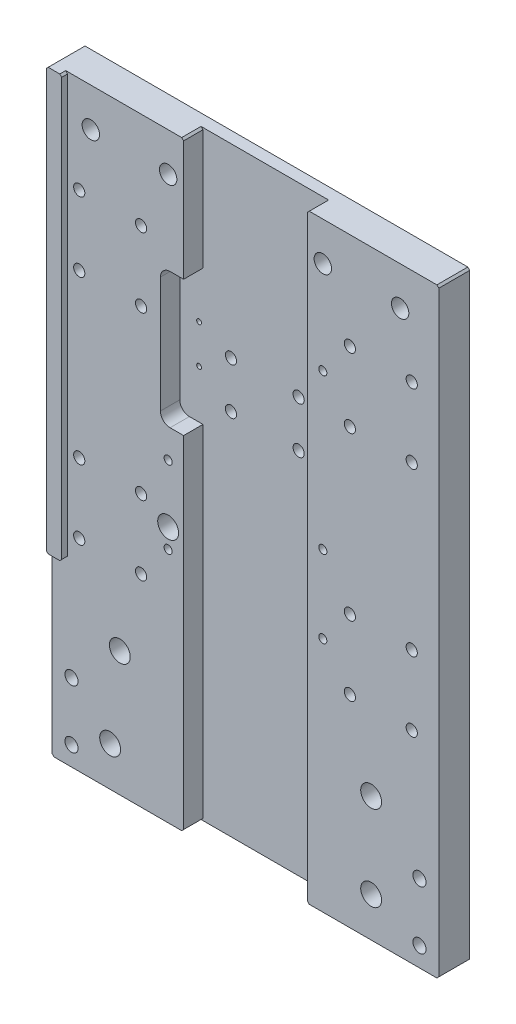
SolidWorks part; units mm, degrees
material "6061-T6 (SS)"
ref_plane "Front Plane" through (0, 0, 0) normal (0, 0, 1) x (1, 0, 0)
ref_plane "Top Plane" through (0, 0, 0) normal (0, 1, 0) x (1, 0, 0)
ref_plane "Right Plane" through (0, 0, 0) normal (1, 0, 0) x (0, 0, -1)
sketch "Sketch1" plane through (0, 0, 0) normal (0, 0, 1) x (1, 0, 0)
  line L0 (0, -10.4775) -> (0, 10.4775) construction
  line L1 (-70, 60) -> (70, 60) construction
  line L2 (-70, 60) -> (-70, -60) construction
  line L3 (-70, -60) -> (70, -60) construction
  line L4 (70, 60) -> (70, -60) construction
  line L5 (-70, 60) -> (70, -60) construction
  line L6 (-70, -60) -> (70, 60) construction
  line L7 (-86, 78) -> (-54, 78) construction
  line L8 (-86, 78) -> (-86, 42) construction
  line L9 (-86, 42) -> (-54, 42) construction
  line L10 (-54, 78) -> (-54, 42) construction
  line L11 (-86, 78) -> (-54, 42) construction
  line L12 (-86, 42) -> (-54, 78) construction
  line L13 (-100, 128) -> (100, 128)
  line L14 (-100, 128) -> (-100, -182.5)
  line L15 (-100, -182.5) -> (100, -182.5)
  line L16 (100, 128) -> (100, -182.5)
  line L17 (-100, -97.5) -> (100, -97.5) construction
  line L18 (-100, 88) -> (100, 88) construction
  line L19 (54, -42) -> (86, -42) construction
  line L20 (54, -42) -> (54, -78) construction
  line L21 (54, -78) -> (86, -78) construction
  line L22 (86, -42) -> (86, -78) construction
  line L23 (54, -42) -> (86, -78) construction
  line L24 (54, -78) -> (86, -42) construction
  line L25 (35.5, -12.5) -> (54.5, -12.5) construction
  line L26 (-17.5, 32) -> (17.5, 32) construction
  line L27 (-17.5, 32) -> (-17.5, 8) construction
  line L28 (-17.5, 8) -> (17.5, 8) construction
  line L29 (17.5, 32) -> (17.5, 8) construction
  line L30 (-17.5, 32) -> (17.5, 8) construction
  line L31 (-17.5, 8) -> (17.5, 32) construction
  line L32 (-100, -97.5) -> (100, -182.5) construction
  point P0 (0, 0)
  point P14 (0, -182.5)
  point P23 (0, 20)
  point P33 (0, -140)
  point P35 (45, -12.5)
  dimension "D1" = 120
  dimension "D2" = 140
  dimension "D3" = 36
  dimension "D4" = 32
  dimension "D5" = 85
  dimension "D6" = 19.5
  dimension "D7" = 40
  dimension "D8" = 10
  dimension "D9" = 200
  dimension "D10" = 24
  dimension "D11" = 35
  dimension "D12" = 20
  dimension "D13" = 19
  dimension "D14" = 45
  dimension "D15" = 47.5
  dimension "D16" = 140
  dimension "D17" = 310.5
extrude "Boss-Extrude1" add sketch "Sketch1" along normal blind 19.05
sketch "Sketch2" plane through (0, 0, 19.05) normal (0, 0, 1) x (1, 0, 0)
  line L0 (100, 128) -> (-100, 128) construction
  line L1 (-92, 128) -> (100, 128)
  line L2 (-92, 128) -> (-92, -90)
  line L3 (-100, -182.5) -> (100, -182.5)
  line L4 (100, 128) -> (100, -182.5)
  line L5 (-92, -90) -> (-100, -90)
  line L6 (-100, 128) -> (-100, -182.5) construction
  line L7 (-70, 60) -> (-70, -60) construction
  line L8 (-100, -90) -> (-100, -182.5)
  line L9 (-70, -60) -> (70, -60) construction
  dimension "D1" = 22
  dimension "D2" = 30
extrude "Cut-Extrude1" cut sketch "Sketch2" against normal offset from surface (3.05 mm away) 16 up to face at (0, -27.25, 0)
sketch "Sketch3" plane through (0, 0, 16) normal (0, 0, 1) x (1, 0, 0)
  line L0 (-100, 128) -> (100, 128) construction
  line L1 (-32, 128) -> (32, 128)
  line L2 (-32, 128) -> (-32, 65)
  line L3 (-32, -182.5) -> (32, -182.5)
  line L4 (32, 128) -> (32, -182.5)
  line L5 (-100, -182.5) -> (100, -182.5) construction
  line L6 (0, -10.4775) -> (0, 10.4775) construction
  line L7 (-32, 65) -> (-39, 65)
  line L8 (-44, 60) -> (-44, 0)
  line L9 (-39, -5) -> (-32, -5)
  line L10 (-32, -5) -> (-32, -182.5)
  line L12 (-34, 40) -> (-34, 20) construction
  line L13 (-44, 30) -> (-34, 30) construction
  arc A0 (-44, 0) -> (-39, -5) centre (-39, 0) ccw
  arc A1 (-39, 65) -> (-44, 60) centre (-39, 60) ccw
  point P8 (0, -182.5)
  point P20 (-44, -5)
  point P23 (-44, 65)
  dimension "D4" = 5
  dimension "D1" = 64
  dimension "D2" = 34
  dimension "D3" = 70
  dimension "D5" = 20
  dimension "D6" = 10
  dimension "D7" = 30
extrude "Cut-Extrude2" cut sketch "Sketch3" against normal blind 10
hole_wizard "M5 Clearance Hole2" positions "Sketch4" profile "Sketch5" hole size "M5" standard "ANSI Metric" end condition up to next
sketch "Sketch4" plane through (0, 0, 16) normal (0, 0, 1) x (1, 0, 0)
  point P0 (54, -42)
  point P3 (86, -42)
  point P6 (86, -78)
  point P9 (54, -78)
sketch "Sketch5" plane through (54, -42, 16) normal (1, 0, 0) x (0, -1, 0)
  line L0 (0, 0) -> (0, 16)
  line L1 (0, 16) -> (2.9, 16)
  line L2 (2.9, 16) -> (2.9, 0)
  line L5 (2.9, 0) -> (0, 0)
  line L11 (0, -6.35) -> (0, 107.95) construction
  dimension "Thru Hole Dia." = 5.8
  dimension "Thru Hole Depth" = 16
mirror "Mirror1" about plane through (0, 0, 0) normal (0, 1, 0) of "M5 Clearance Hole2"
hole_wizard "M8 Clearance Hole1" positions "Sketch13" profile "Sketch14" hole size "M8" standard "ANSI Metric" end condition up to next
sketch "Sketch13" plane through (0, 0, 16) normal (0, 0, 1) x (1, 0, 0)
  line L0 (40, 108) -> (80, 108)
  line L2 (-100, 88) -> (100, 88) construction
  line L3 (0, -10.4775) -> (0, 10.4775) construction
  point P1 (40, 108)
  point P2 (80, 108)
  dimension "D1" = 20
  dimension "D2" = 40
  dimension "D3" = 40
sketch "Sketch14" plane through (40, 108, 16) normal (1, 0, 0) x (0, -1, 0)
  line L0 (0, 0) -> (0, 16)
  line L1 (0, 16) -> (4.5, 16)
  line L2 (4.5, 16) -> (4.5, 0)
  line L5 (4.5, 0) -> (0, 0)
  line L11 (0, -6.35) -> (0, 107.95) construction
  dimension "Thru Hole Dia." = 9
  dimension "Thru Hole Depth" = 16
hole_wizard "M5x0.8 Tapped Hole1" positions "Sketch15" profile "Sketch16" tap size "M5x0.8" standard "ANSI Metric" end condition up to next
sketch "Sketch15" plane through (0, 0, 16) normal (0, 0, 1) x (1, 0, 0)
  line L0 (40, 60) -> (40, -20)
  line L1 (40, -20) -> (40, -60)
  line L3 (-70, -60) -> (70, -60) construction
  line L4 (-70, 60) -> (70, 60) construction
  point P0 (40, 60)
  point P1 (40, -20)
  point P3 (40, -60)
  dimension "D1" = 40
  dimension "D2" = 80
  dimension "D3" = 40
sketch "Sketch16" plane through (40, 60, 16) normal (1, 0, 0) x (0, -1, 0)
  line L0 (0, 0) -> (0, 16)
  line L1 (0, 16) -> (2.1, 16)
  line L2 (2.1, 16) -> (2.1, 0)
  line L5 (2.1, 0) -> (0, 0)
  line L11 (0, -6.35) -> (0, 107.95) construction
  dimension "Thru Tap Drill Dia." = 4.2
  dimension "Thru Tap Drill Depth" = 16
cosmetic thread "Hole Thread5" parameters "D2"=5
cosmetic thread "Hole Thread6" parameters "D2"=5
cosmetic thread "Hole Thread7" parameters "D2"=5
mirror "Mirror2" about plane through (0, 0, 0) normal (1, 0, 0) of "M5x0.8 Tapped Hole1", "M8 Clearance Hole1", "Mirror1"
cosmetic thread "Hole Thread8" parameters "D2"=5
cosmetic thread "Hole Thread9" parameters "D2"=5
cosmetic thread "Hole Thread10" parameters "D2"=5
hole_wizard "M5 Clearance Hole1" positions "Sketch11" profile "Sketch12" hole size "M5" standard "ANSI Metric" end condition up to next
sketch "Sketch11" plane through (0, 0, 6) normal (0, 0, 1) x (1, 0, 0)
  point P0 (-17.5, 32)
  point P3 (17.5, 32)
  point P6 (17.5, 8)
  point P9 (-17.5, 8)
sketch "Sketch12" plane through (-17.5, 32, 6) normal (1, 0, 0) x (0, -1, 0)
  line L0 (0, 0) -> (0, 6)
  line L1 (0, 6) -> (2.9, 6)
  line L2 (2.9, 6) -> (2.9, 0)
  line L5 (2.9, 0) -> (0, 0)
  line L11 (0, -6.35) -> (0, 107.95) construction
  dimension "Thru Hole Dia." = 5.8
  dimension "Thru Hole Depth" = 6
hole_wizard "M12x1.25 Tapped Hole2" positions "Sketch17" profile "Sketch18" tap size "M12x1.25" standard "ANSI Metric" end condition up to next
sketch "Sketch17" plane through (0, 0, 16) normal (0, 0, 1) x (1, 0, 0)
  line L1 (-65, -118) -> (65, -118)
  line L2 (-65, -118) -> (-65, -162)
  line L3 (-65, -162) -> (65, -162)
  line L4 (65, -118) -> (65, -162)
  line L5 (-65, -118) -> (65, -162) construction
  line L6 (-65, -162) -> (65, -118) construction
  line L7 (-65, -162) -> (-70, -162)
  point P2 (65, -162)
  point P63 (-65, -118)
  point P65 (65, -118)
  point P72 (-70, -162)
  dimension "D1" = 44
  dimension "D2" = 130
  dimension "D3" = 5
sketch "Sketch18" plane through (65, -162, 16) normal (1, 0, 0) x (0, -1, 0)
  line L0 (0, 0) -> (0, 16)
  line L1 (0, 16) -> (5.4, 16)
  line L2 (5.4, 16) -> (5.4, 0)
  line L5 (5.4, 0) -> (0, 0)
  line L11 (0, -6.35) -> (0, 107.95) construction
  dimension "Thru Tap Drill Dia." = 10.8
  dimension "Thru Tap Drill Depth" = 16
cosmetic thread "Hole Thread11" parameters "D2"=12
cosmetic thread "Hole Thread12" parameters "D2"=12
cosmetic thread "Hole Thread13" parameters "D2"=12
cosmetic thread "Hole Thread14" parameters "D2"=12
hole_wizard "M8x1.25 Tapped Hole1" positions "Sketch20" profile "Sketch21" tap size "M8x1.25" standard "ANSI Metric" end condition up to next
sketch "Sketch20" plane through (0, 0, 0) normal (0, 0, -1) x (-1, 0, 0)
  line L1 (-90, -142.5) -> (90, -142.5)
  line L2 (-90, -142.5) -> (-90, -172.5)
  line L3 (-90, -172.5) -> (90, -172.5)
  line L4 (90, -142.5) -> (90, -172.5)
  line L5 (0, 10.4775) -> (0, -10.4775) construction
  line L6 (100, -182.5) -> (-100, -182.5) construction
  point P1 (-90, -142.5)
  point P2 (90, -172.5)
  point P205 (-90, -172.5)
  point P206 (90, -142.5)
  point P208 (0, -142.5)
  dimension "D1" = 180
  dimension "D2" = 10
  dimension "D3" = 30
sketch "Sketch21" plane through (90, -142.5, 0) normal (1, 0, 0) x (0, 1, 0)
  line L0 (0, 0) -> (0, 16)
  line L1 (0, 16) -> (3.4, 16)
  line L2 (3.4, 16) -> (3.4, 0)
  line L5 (3.4, 0) -> (0, 0)
  line L11 (0, -6.35) -> (0, 107.95) construction
  dimension "Thru Tap Drill Dia." = 6.8
  dimension "Thru Tap Drill Depth" = 16
cosmetic thread "Hole Thread15" parameters "D2"=8
cosmetic thread "Hole Thread16" parameters "D2"=8
cosmetic thread "Hole Thread17" parameters "D2"=8
cosmetic thread "Hole Thread18" parameters "D2"=8
hole_wizard "M3x0.5 Tapped Hole1" positions "Sketch22" profile "Sketch23" tap size "M3x0.5" standard "ANSI Metric" end condition up to next
sketch "Sketch22" plane through (0, 0, 6) normal (0, 0, 1) x (1, 0, 0)
  point P1 (-34, 40)
  point P2 (-34, 20)
sketch "Sketch23" plane through (-34, 40, 6) normal (1, 0, 0) x (0, -1, 0)
  line L0 (0, 0) -> (0, 6)
  line L1 (0, 6) -> (1.25, 6)
  line L2 (1.25, 6) -> (1.25, 0)
  line L5 (1.25, 0) -> (0, 0)
  line L11 (0, -6.35) -> (0, 107.95) construction
  dimension "Thru Tap Drill Dia." = 2.5
  dimension "Thru Tap Drill Depth" = 6
cosmetic thread "Hole Thread19" parameters "D2"=3
cosmetic thread "Hole Thread20" parameters "D2"=3
hole_wizard "M12x1.25 Tapped Hole1" positions "Sketch24" profile "Sketch25" tap size "M12x1.25" standard "ANSI Metric" end condition up to next
sketch "Sketch24" plane through (0, 0, 16) normal (0, 0, 1) x (1, 0, 0)
  line L0 (0, -10.4775) -> (0, 10.4775) construction
  point P0 (-40, -50)
  dimension "D1" = 40
  dimension "D2" = 50
sketch "Sketch25" plane through (-40, -50, 16) normal (1, 0, 0) x (0, -1, 0)
  line L0 (0, 0) -> (0, 16)
  line L1 (0, 16) -> (5.4, 16)
  line L2 (5.4, 16) -> (5.4, 0)
  line L5 (5.4, 0) -> (0, 0)
  line L11 (0, -6.35) -> (0, 107.95) construction
  dimension "Thru Tap Drill Dia." = 10.8
  dimension "Thru Tap Drill Depth" = 16
cosmetic thread "Hole Thread21" parameters "D2"=12
chamfer "Chamfer1" distance 1 11 edges at (100, 128, 8) (32, 128, 11) (-32, 128, 11) (-92, 128, 17.525) (-100, 128, 9.525) (32, -182.5, 11) (100, -182.5, 8) (-100, -182.5, 8) (-100, -90, 17.525) (-92, -90, 17.525) (-32, -182.5, 11)
